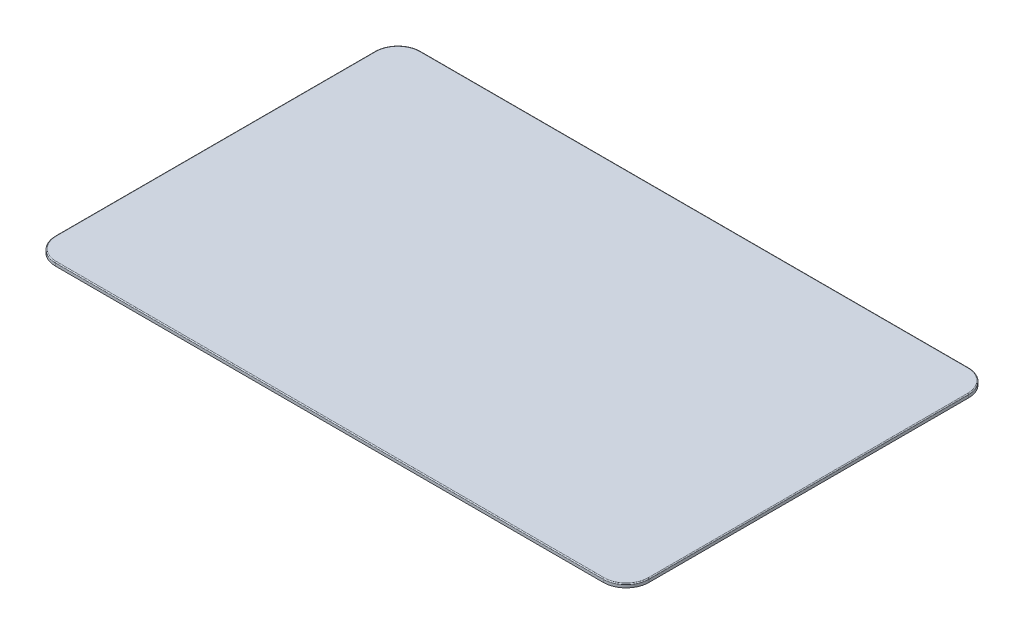
SolidWorks part; units mm, degrees
ref_plane "Спереди" through (0, 0, 0) normal (0, 0, 1) x (1, 0, 0)
ref_plane "Сверху" through (0, 0, 0) normal (0, 1, 0) x (1, 0, 0)
ref_plane "Справа" through (0, 0, 0) normal (1, 0, 0) x (0, 0, -1)
sketch "Эскиз1" plane through (0, 0, 0) normal (0, 1, 0) x (1, 0, 0)
  line L1 (-600, -400) -> (600, -400)
  line L2 (-650, -350) -> (-650, 350)
  line L3 (-600, 400) -> (600, 400)
  line L4 (650, -350) -> (650, 350)
  line L5 (-650, -400) -> (650, 400) construction
  line L6 (-650, 400) -> (650, -400) construction
  arc A0 (-600, 400) -> (-650, 350) centre (-600, 350) ccw
  arc A1 (600, 400) -> (650, 350) centre (600, 350) cw
  arc A2 (650, -350) -> (600, -400) centre (600, -350) cw
  arc A3 (-600, -400) -> (-650, -350) centre (-600, -350) cw
  point P0 (0, 0)
  dimension "D1" = 50
  dimension "D4" = 50
  dimension "D2" = 1300
  dimension "D3" = 800
extrude "Бобышка-Вытянуть1" add sketch "Эскиз1" along normal blind 8
fillet "Скругление1" radius 2 8 edges at (-635.3553, 8, -385.3553) (0, 8, -400) (635.3553, 8, -385.3553) (650, 8, 0) (635.3553, 8, 385.3553) (0, 8, 400) (-635.3553, 8, 385.3553) (-650, 8, 0)
sketch "Эскиз2" plane through (0, 0, 0) normal (0, -1, 0) x (1, 0, 0)
  line L0 (0, 398) -> (0, 115.0711) construction
  line L1 (-498, -35) -> (-405.9312, -35) construction
  line L2 (-494.82, 35) -> (-402.7512, 35) construction
  line L3 (-498, -100.1909) -> (-498, 80.8489) construction
  line L4 (-505.5, -118.7139) -> (-423, -118.7139)
  line L5 (-480.5, -93.7139) -> (-448, -93.7139)
  line L6 (-418, 113.7139) -> (-418, 29.5)
  line L7 (250, 398) -> (250, -398) construction
  line L8 (-250, 398) -> (-250, -398) construction
  line L9 (-648, 0) -> (648, 0) construction
  line L10 (302.5206, -212.9276) -> (307.7592, -212.906)
  line L12 (259.7408, -280.6043) -> (259.7408, -218.094)
  line L13 (262.2408, -283.1043) -> (308.0492, -283.1043)
  line L14 (265.5, -179.2861) -> (207.5, -179.2861)
  line L15 (-505.5, 118.7139) -> (-423, 118.7139)
  line L16 (-443, 88.7139) -> (-443, -88.7139)
  line L17 (-480.5, 93.7139) -> (-448, 93.7139)
  line L18 (-485.5, 84.9278) -> (-485.5, 88.7139)
  line L19 (-510.5, 85.0723) -> (-510.5, 113.7139)
  line L20 (-523.5388, 12.3957) -> (-523.2695, 77.6043)
  line L21 (403, -14.5) -> (302.5, -14.5)
  line L22 (403, 14.5) -> (302.5, 14.5)
  line L23 (418, -29.5) -> (418, -113.7139)
  line L24 (265.5, 174.2861) -> (207.5, 174.2861)
  line L25 (-515.5206, -80.0724) -> (-520.7592, -80.094)
  line L27 (270.5, -174.2861) -> (270.5, 169.2861)
  line L28 (197.4794, 212.9276) -> (192.2408, 212.906)
  line L29 (240.2592, 280.6043) -> (240.2592, 218.125)
  line L31 (237.7592, 283.1043) -> (191.9508, 283.1043)
  line L32 (250, 213.1446) -> (245.2798, 213.1251)
  line L33 (310.5388, -280.6043) -> (310.2695, -215.3957)
  line L34 (-472.7408, -12.3957) -> (-472.7408, -77.3957)
  line L35 (297.5, -207.9277) -> (297.5, -19.5)
  line L36 (202.5, -207.9277) -> (202.5, -184.2861)
  line L37 (-475.2408, 79.906) -> (-480.5206, 79.9278)
  line L38 (-302.5206, 212.9276) -> (-307.7592, 212.906)
  line L39 (-265.5, 179.2861) -> (-207.5, 179.2861)
  line L40 (-259.7408, 280.6043) -> (-259.7408, 218.1043)
  line L41 (189.4612, -280.6043) -> (189.7305, -215.3957)
  line L42 (-262.2408, 283.1043) -> (-308.0492, 283.1043)
  line L43 (-254.7408, 213.1043) -> (-245.2592, 213.1043)
  line L44 (237.7592, -283.1043) -> (191.9508, -283.1043)
  line L46 (240.2592, -280.6043) -> (240.2592, -218.094)
  line L47 (197.4794, -212.9276) -> (192.2408, -212.906)
  line L50 (-310.5388, 280.6043) -> (-310.2695, 215.3957)
  line L51 (-297.5, 207.9277) -> (-297.5, 14.5)
  line L52 (-202.5, 207.9277) -> (-202.5, 184.2861)
  line L53 (-189.4612, 280.6043) -> (-189.7305, 215.3957)
  line L54 (-265.5, -174.2861) -> (-207.5, -174.2861)
  line L56 (-475.2408, -9.8957) -> (-521.0492, -9.8957)
  line L57 (-475.2408, -79.906) -> (-480.5206, -79.9278)
  line L58 (-475.2408, 9.8957) -> (-521.0492, 9.8957)
  line L59 (-523.5388, -12.3957) -> (-523.2695, -77.6043)
  line L60 (-510.5, -85.0723) -> (-510.5, -113.7139)
  line L61 (-472.7408, 12.3957) -> (-472.7408, 77.3957)
  line L62 (-515.5206, 80.0724) -> (-520.7592, 80.094)
  line L63 (-485.5, -84.9278) -> (-485.5, -88.7139)
  line L65 (-197.4794, -212.9276) -> (-192.2408, -212.906)
  line L66 (-240.2592, -280.6043) -> (-240.2592, -218.125)
  line L68 (-237.7592, -283.1043) -> (-191.9508, -283.1043)
  line L69 (-250, -213.1446) -> (-245.2798, -213.1251)
  line L70 (485.5, -84.9278) -> (485.5, -88.7139)
  line L71 (-189.4612, -280.6043) -> (-189.7305, -215.3957)
  line L72 (-202.5, -207.9277) -> (-202.5, -179.2861)
  line L73 (-297.5, -207.9277) -> (-297.5, -14.5)
  line L74 (515.5206, 80.0724) -> (520.7592, 80.094)
  line L75 (472.7408, 12.3957) -> (472.7408, 77.3957)
  line L76 (510.5, -85.0723) -> (510.5, -113.7139)
  line L77 (523.5388, -12.3957) -> (523.2695, -77.6043)
  line L78 (475.2408, 9.8957) -> (521.0492, 9.8957)
  line L79 (475.2408, -79.906) -> (480.5206, -79.9278)
  line L80 (475.2408, -9.8957) -> (521.0492, -9.8957)
  line L81 (-102.1767, 35.0711) -> (-96.9381, 35.0927)
  line L82 (-142.4565, 34.9047) -> (-137.1767, 34.9265)
  line L83 (-94.1585, -32.6057) -> (-94.4278, 32.603)
  line L84 (-144.9565, -32.6056) -> (-144.9565, 32.3944)
  line L85 (-142.4565, -35.1056) -> (-96.6482, -35.1056)
  line L86 (-42.1767, 35.0711) -> (-36.9381, 35.0927)
  line L87 (-82.4565, 34.9047) -> (-77.1767, 34.9265)
  line L88 (-34.1585, -32.6057) -> (-34.4278, 32.603)
  line L89 (-84.9565, -32.6056) -> (-84.9565, 32.3944)
  line L90 (-82.4565, -35.1056) -> (-36.6482, -35.1056)
  line L91 (17.8233, 35.0711) -> (23.0619, 35.0927)
  line L92 (-22.4565, 34.9047) -> (-17.1767, 34.9265)
  line L93 (25.8415, -32.6057) -> (25.5722, 32.603)
  line L94 (-24.9565, -32.6056) -> (-24.9565, 32.3944)
  line L95 (-22.4565, -35.1056) -> (23.3518, -35.1056)
  line L96 (77.8233, 35.0711) -> (83.0619, 35.0927)
  line L97 (37.5435, 34.9047) -> (42.8233, 34.9265)
  line L98 (85.8415, -32.6057) -> (85.5722, 32.603)
  line L99 (35.0435, -32.6056) -> (35.0435, 32.3944)
  line L100 (37.5435, -35.1056) -> (83.3518, -35.1056)
  line L101 (137.9695, 35.0717) -> (143.0619, 35.0927)
  line L102 (97.5435, 34.9047) -> (102.0709, 34.9234)
  line L103 (145.8415, -32.6057) -> (145.5722, 32.603)
  line L104 (95.0435, -32.6056) -> (95.0435, 32.3944)
  line L105 (97.5435, -35.1056) -> (143.3518, -35.1056)
  line L106 (-132.1973, 39.9265) -> (-132.1973, 110.0711)
  line L107 (-107.1973, 40.071) -> (-107.1973, 85.0711)
  line L108 (0, 0) -> (0, -400) construction
  line L109 (67.8027, 80.0711) -> (17.8027, 80.0711)
  line L110 (107.1973, 40.071) -> (107.1973, 85.0711)
  line L112 (-310.5388, -280.6043) -> (-310.2695, -215.3957)
  line L114 (-237.7592, 283.1043) -> (-191.9508, 283.1043)
  line L116 (-240.2592, 280.6043) -> (-240.2592, 218.1043)
  line L117 (-197.4794, 212.9276) -> (-192.2408, 212.906)
  line L118 (-270.5, 174.2861) -> (-270.5, -169.2861)
  line L122 (-418, -29.5) -> (-418, -113.7139)
  line L123 (189.4612, 280.6043) -> (189.7305, 215.3957)
  line L124 (202.5, 207.9277) -> (202.5, 179.2861)
  line L125 (297.5, 207.9277) -> (297.5, 19.5)
  line L126 (310.5388, 280.6043) -> (310.2695, 215.3957)
  line L127 (250, 213.1446) -> (254.7202, 213.1251)
  line L128 (262.2408, 283.1043) -> (308.0492, 283.1043)
  line L129 (259.7408, 280.6043) -> (259.7408, 218.125)
  line L131 (302.5206, 212.9276) -> (307.7592, 212.906)
  line L132 (498, -100.1909) -> (498, 80.8489) construction
  line L133 (475.2408, 79.906) -> (480.5206, 79.9278)
  line L134 (472.7408, -12.3957) -> (472.7408, -77.3957)
  line L135 (515.5206, -80.0724) -> (520.7592, -80.094)
  line L136 (523.5388, 12.3957) -> (523.2695, 77.6043)
  line L137 (-403, 14.5) -> (-297.5, 14.5)
  line L138 (-403, -14.5) -> (-297.5, -14.5)
  line L139 (-250, -213.1446) -> (-254.7202, -213.1251)
  line L140 (510.5, 85.0723) -> (510.5, 113.7139)
  line L141 (485.5, 84.9278) -> (485.5, 88.7139)
  line L142 (-262.2408, -283.1043) -> (-308.0492, -283.1043)
  line L143 (494.82, 35) -> (402.7512, 35) construction
  line L144 (498, -35) -> (405.9312, -35) construction
  line L145 (480.5, 93.7139) -> (448, 93.7139)
  line L146 (443, 88.7139) -> (443, -88.7139)
  line L147 (505.5, 118.7139) -> (423, 118.7139)
  line L148 (418, 113.7139) -> (418, 29.5)
  line L149 (480.5, -93.7139) -> (448, -93.7139)
  line L150 (-259.7408, -280.6043) -> (-259.7408, -218.125)
  line L151 (505.5, -118.7139) -> (423, -118.7139)
  line L153 (-302.5206, -212.9276) -> (-307.7592, -212.906)
  line L154 (72.8027, 40.071) -> (72.8027, 50.0711)
  line L155 (47.8027, 39.9265) -> (47.8027, 50.0711)
  line L156 (12.8027, 40.071) -> (12.8027, 50.0711)
  line L157 (-12.1973, 39.9265) -> (-12.1973, 50.0711)
  line L158 (-47.1973, 40.071) -> (-47.1973, 50.0711)
  line L159 (-72.1973, 39.9265) -> (-72.1973, 50.0711)
  line L160 (254.7408, -213.094) -> (245.2592, -213.094)
  line L161 (42.8027, 55.0711) -> (17.8027, 55.0711)
  line L162 (-17.1973, 55.0711) -> (-42.1973, 55.0711)
  line L163 (102.1973, 90.0711) -> (17.1973, 90.0711)
  line L164 (72.8027, 50.0711) -> (72.8027, 75.0711)
  line L165 (-72.1973, 50.0711) -> (-72.1973, 75.0711)
  line L166 (127.8027, 115.0711) -> (-127.1973, 115.0711)
  line L167 (-102.1973, 90.0711) -> (-17.1973, 90.0711)
  line L170 (-17.1973, 80.0711) -> (-67.1973, 80.0711)
  line L171 (132.8027, 40.071) -> (132.8027, 110.0711)
  arc A0 (240.2592, -218.094) -> (245.2592, -213.094) centre (245.2592, -218.094) cw
  arc A1 (297.5, -207.9277) -> (302.5206, -212.9276) centre (302.5, -207.9277) ccw
  arc A2 (310.2695, -215.3957) -> (307.7592, -212.906) centre (310.2592, -212.8957) ccw
  arc A3 (259.7408, 218.125) -> (254.7202, 213.1251) centre (254.7408, 218.125) cw
  arc A4 (245.2798, 213.1251) -> (240.2592, 218.125) centre (245.2592, 218.125) cw
  arc A5 (202.5, -184.2861) -> (207.5, -179.2861) centre (207.5, -184.2861) cw
  arc A6 (308.0492, -283.1043) -> (310.5388, -280.6043) centre (310.5492, -283.1043) ccw
  arc A7 (259.7408, -280.6043) -> (262.2408, -283.1043) centre (259.7408, -283.1043) ccw
  arc A8 (240.2592, -280.6043) -> (237.7592, -283.1043) centre (240.2592, -283.1043) cw
  arc A9 (191.9508, -283.1043) -> (189.4612, -280.6043) centre (189.4508, -283.1043) cw
  arc A10 (270.5, 169.2861) -> (265.5, 174.2861) centre (265.5, 169.2861) ccw
  arc A11 (510.5, 113.7139) -> (505.5, 118.7139) centre (505.5, 113.7139) ccw
  arc A12 (265.5, -179.2861) -> (270.5, -174.2861) centre (265.5, -174.2861) ccw
  arc A13 (189.7305, -215.3957) -> (192.2408, -212.906) centre (189.7408, -212.8957) cw
  arc A14 (202.5, -207.9277) -> (197.4794, -212.9276) centre (197.5, -207.9277) cw
  arc A15 (254.7408, -213.094) -> (259.7408, -218.094) centre (254.7408, -218.094) cw
  arc A16 (-240.2592, 218.1043) -> (-245.2592, 213.1043) centre (-245.2592, 218.1043) cw
  arc A17 (505.5, -118.7139) -> (510.5, -113.7139) centre (505.5, -113.7139) ccw
  arc A18 (-254.7408, 213.1043) -> (-259.7408, 218.1043) centre (-254.7408, 218.1043) cw
  arc A19 (-202.5, 184.2861) -> (-207.5, 179.2861) centre (-207.5, 184.2861) cw
  arc A20 (413, 24.5) -> (418, 29.5) centre (413, 29.5) ccw
  arc A21 (202.5, 207.9277) -> (197.4794, 212.9276) centre (197.5, 207.9277) ccw
  arc A22 (189.7305, 215.3957) -> (192.2408, 212.906) centre (189.7408, 212.8957) ccw
  arc A23 (403, 14.5) -> (408, 19.5) centre (403, 19.5) ccw
  arc A24 (191.9508, 283.1043) -> (189.4612, 280.6043) centre (189.4508, 283.1043) ccw
  arc A25 (240.2592, 280.6043) -> (237.7592, 283.1043) centre (240.2592, 283.1043) ccw
  arc A26 (259.7408, 280.6043) -> (262.2408, 283.1043) centre (259.7408, 283.1043) cw
  arc A27 (308.0492, 283.1043) -> (310.5388, 280.6043) centre (310.5492, 283.1043) cw
  arc A28 (413, 24.5) -> (408, 19.5) centre (413, 19.5) ccw
  arc A29 (310.2695, 215.3957) -> (307.7592, 212.906) centre (310.2592, 212.8957) cw
  arc A30 (297.5, 207.9277) -> (302.5206, 212.9276) centre (302.5, 207.9277) cw
  arc A31 (413, -24.5) -> (408, -19.5) centre (413, -19.5) cw
  arc A32 (202.5, 179.2861) -> (207.5, 174.2861) centre (207.5, 179.2861) ccw
  arc A33 (-270.5, -169.2861) -> (-265.5, -174.2861) centre (-265.5, -169.2861) ccw
  arc A34 (485.5, 88.7139) -> (480.5, 93.7139) centre (480.5, 88.7139) ccw
  arc A35 (-443, -88.7139) -> (-448, -93.7139) centre (-448, -88.7139) cw
  arc A36 (480.5206, 79.9278) -> (485.5, 84.9278) centre (480.5, 84.9278) ccw
  arc A37 (510.5, 85.0723) -> (515.5206, 80.0724) centre (515.5, 85.0723) ccw
  arc A38 (472.7408, -12.3957) -> (475.2408, -9.8957) centre (472.7408, -9.8957) cw
  arc A39 (521.0492, -9.8957) -> (523.5388, -12.3957) centre (523.5492, -9.8957) cw
  arc A40 (475.2408, -79.906) -> (472.7408, -77.3957) centre (472.7408, -79.8957) cw
  arc A41 (523.2695, -77.6043) -> (520.7592, -80.094) centre (523.2592, -80.1043) cw
  arc A42 (510.5, -85.0723) -> (515.5206, -80.0724) centre (515.5, -85.0723) cw
  arc A43 (480.5206, -79.9278) -> (485.5, -84.9278) centre (480.5, -84.9278) cw
  arc A44 (523.2695, 77.6043) -> (520.7592, 80.094) centre (523.2592, 80.1043) ccw
  arc A45 (-418, -113.7139) -> (-423, -118.7139) centre (-423, -113.7139) cw
  arc A46 (485.5, -88.7139) -> (480.5, -93.7139) centre (480.5, -88.7139) cw
  arc A47 (475.2408, 79.906) -> (472.7408, 77.3957) centre (472.7408, 79.8957) ccw
  arc A48 (521.0492, 9.8957) -> (523.5388, 12.3957) centre (523.5492, 9.8957) ccw
  arc A49 (472.7408, 12.3957) -> (475.2408, 9.8957) centre (472.7408, 9.8957) ccw
  arc A50 (-443, 88.7139) -> (-448, 93.7139) centre (-448, 88.7139) ccw
  arc A51 (-418, 113.7139) -> (-423, 118.7139) centre (-423, 113.7139) ccw
  arc A52 (418, 113.7139) -> (423, 118.7139) centre (423, 113.7139) cw
  arc A53 (443, 88.7139) -> (448, 93.7139) centre (448, 88.7139) cw
  arc A54 (418, -113.7139) -> (423, -118.7139) centre (423, -113.7139) ccw
  arc A55 (443, -88.7139) -> (448, -93.7139) centre (448, -88.7139) ccw
  arc A56 (-472.7408, 12.3957) -> (-475.2408, 9.8957) centre (-472.7408, 9.8957) cw
  arc A57 (-521.0492, 9.8957) -> (-523.5388, 12.3957) centre (-523.5492, 9.8957) cw
  arc A58 (-475.2408, 79.906) -> (-472.7408, 77.3957) centre (-472.7408, 79.8957) cw
  arc A59 (-485.5, -88.7139) -> (-480.5, -93.7139) centre (-480.5, -88.7139) ccw
  arc A60 (-523.2695, 77.6043) -> (-520.7592, 80.094) centre (-523.2592, 80.1043) cw
  arc A61 (-480.5206, -79.9278) -> (-485.5, -84.9278) centre (-480.5, -84.9278) ccw
  arc A62 (-510.5, -85.0723) -> (-515.5206, -80.0724) centre (-515.5, -85.0723) ccw
  arc A63 (-523.2695, -77.6043) -> (-520.7592, -80.094) centre (-523.2592, -80.1043) ccw
  arc A64 (-475.2408, -79.906) -> (-472.7408, -77.3957) centre (-472.7408, -79.8957) ccw
  arc A65 (-521.0492, -9.8957) -> (-523.5388, -12.3957) centre (-523.5492, -9.8957) ccw
  arc A66 (-472.7408, -12.3957) -> (-475.2408, -9.8957) centre (-472.7408, -9.8957) ccw
  arc A67 (-510.5, 85.0723) -> (-515.5206, 80.0724) centre (-515.5, 85.0723) cw
  arc A68 (-480.5206, 79.9278) -> (-485.5, 84.9278) centre (-480.5, 84.9278) cw
  arc A69 (-485.5, 88.7139) -> (-480.5, 93.7139) centre (-480.5, 88.7139) cw
  arc A70 (-202.5, -179.2861) -> (-207.5, -174.2861) centre (-207.5, -179.2861) ccw
  arc A71 (-270.5, 174.2861) -> (-265.5, 179.2861) centre (-265.5, 174.2861) cw
  arc A72 (297.5, 19.5) -> (302.5, 14.5) centre (302.5, 19.5) ccw
  arc A73 (-297.5, 207.9277) -> (-302.5206, 212.9276) centre (-302.5, 207.9277) ccw
  arc A74 (-310.2695, 215.3957) -> (-307.7592, 212.906) centre (-310.2592, 212.8957) ccw
  arc A75 (297.5, -19.5) -> (302.5, -14.5) centre (302.5, -19.5) cw
  arc A76 (-308.0492, 283.1043) -> (-310.5388, 280.6043) centre (-310.5492, 283.1043) ccw
  arc A77 (-259.7408, 280.6043) -> (-262.2408, 283.1043) centre (-259.7408, 283.1043) ccw
  arc A78 (-240.2592, 280.6043) -> (-237.7592, 283.1043) centre (-240.2592, 283.1043) cw
  arc A79 (-191.9508, 283.1043) -> (-189.4612, 280.6043) centre (-189.4508, 283.1043) cw
  arc A80 (-418, -29.5) -> (-413, -24.5) centre (-413, -29.5) cw
  arc A81 (-189.7305, 215.3957) -> (-192.2408, 212.906) centre (-189.7408, 212.8957) cw
  arc A82 (-202.5, 207.9277) -> (-197.4794, 212.9276) centre (-197.5, 207.9277) cw
  arc A83 (-403, -14.5) -> (-408, -19.5) centre (-403, -19.5) ccw
  arc A84 (-240.2592, -218.125) -> (-245.2798, -213.1251) centre (-245.2592, -218.125) ccw
  arc A85 (-254.7202, -213.1251) -> (-259.7408, -218.125) centre (-254.7408, -218.125) ccw
  arc A86 (-505.5, -118.7139) -> (-510.5, -113.7139) centre (-505.5, -113.7139) cw
  arc A87 (403, -14.5) -> (408, -19.5) centre (403, -19.5) cw
  arc A88 (413, -24.5) -> (418, -29.5) centre (413, -29.5) cw
  arc A89 (-202.5, -207.9277) -> (-197.4794, -212.9276) centre (-197.5, -207.9277) ccw
  arc A90 (-189.7305, -215.3957) -> (-192.2408, -212.906) centre (-189.7408, -212.8957) ccw
  arc A91 (-418, 29.5) -> (-413, 24.5) centre (-413, 29.5) ccw
  arc A92 (-510.5, 113.7139) -> (-505.5, 118.7139) centre (-505.5, 113.7139) cw
  arc A93 (-403, 14.5) -> (-408, 19.5) centre (-403, 19.5) cw
  arc A94 (-191.9508, -283.1043) -> (-189.4612, -280.6043) centre (-189.4508, -283.1043) ccw
  arc A95 (-240.2592, -280.6043) -> (-237.7592, -283.1043) centre (-240.2592, -283.1043) ccw
  arc A96 (-259.7408, -280.6043) -> (-262.2408, -283.1043) centre (-259.7408, -283.1043) cw
  arc A97 (-308.0492, -283.1043) -> (-310.5388, -280.6043) centre (-310.5492, -283.1043) cw
  arc A98 (-408, 19.5) -> (-413, 24.5) centre (-413, 19.5) ccw
  arc A99 (-413, -24.5) -> (-408, -19.5) centre (-413, -19.5) ccw
  arc A101 (-310.2695, -215.3957) -> (-307.7592, -212.906) centre (-310.2592, -212.8957) cw
  arc A102 (-297.5, -207.9277) -> (-302.5206, -212.9276) centre (-302.5, -207.9277) cw
  arc A104 (-137.1767, 34.9265) -> (-132.1973, 39.9265) centre (-137.1973, 39.9265) ccw
  arc A105 (-144.9565, -32.6056) -> (-142.4565, -35.1056) centre (-144.9565, -35.1056) ccw
  arc A106 (-107.1973, 40.071) -> (-102.1767, 35.0711) centre (-102.1973, 40.071) ccw
  arc A107 (-94.4278, 32.603) -> (-96.9381, 35.0927) centre (-94.4381, 35.103) ccw
  arc A108 (-142.4565, 34.9047) -> (-144.9565, 32.3944) centre (-144.9565, 34.8944) ccw
  arc A109 (-96.6482, -35.1056) -> (-94.1585, -32.6057) centre (-94.1482, -35.1056) ccw
  arc A110 (-77.1767, 34.9265) -> (-72.1973, 39.9265) centre (-77.1973, 39.9265) ccw
  arc A111 (-84.9565, -32.6056) -> (-82.4565, -35.1056) centre (-84.9565, -35.1056) ccw
  arc A112 (-47.1973, 40.071) -> (-42.1767, 35.0711) centre (-42.1973, 40.071) ccw
  arc A113 (-34.4278, 32.603) -> (-36.9381, 35.0927) centre (-34.4381, 35.103) ccw
  arc A114 (-82.4565, 34.9047) -> (-84.9565, 32.3944) centre (-84.9565, 34.8944) ccw
  arc A115 (-36.6482, -35.1056) -> (-34.1585, -32.6057) centre (-34.1482, -35.1056) ccw
  arc A116 (-17.1767, 34.9265) -> (-12.1973, 39.9265) centre (-17.1973, 39.9265) ccw
  arc A117 (-24.9565, -32.6056) -> (-22.4565, -35.1056) centre (-24.9565, -35.1056) ccw
  arc A118 (12.8027, 40.071) -> (17.8233, 35.0711) centre (17.8027, 40.071) ccw
  arc A119 (25.5722, 32.603) -> (23.0619, 35.0927) centre (25.5619, 35.103) ccw
  arc A120 (-22.4565, 34.9047) -> (-24.9565, 32.3944) centre (-24.9565, 34.8944) ccw
  arc A121 (23.3518, -35.1056) -> (25.8415, -32.6057) centre (25.8518, -35.1056) ccw
  arc A122 (42.8233, 34.9265) -> (47.8027, 39.9265) centre (42.8027, 39.9265) ccw
  arc A123 (35.0435, -32.6056) -> (37.5435, -35.1056) centre (35.0435, -35.1056) ccw
  arc A124 (72.8027, 40.071) -> (77.8233, 35.0711) centre (77.8027, 40.071) ccw
  arc A125 (85.5722, 32.603) -> (83.0619, 35.0927) centre (85.5619, 35.103) ccw
  arc A126 (37.5435, 34.9047) -> (35.0435, 32.3944) centre (35.0435, 34.8944) ccw
  arc A127 (83.3518, -35.1056) -> (85.8415, -32.6057) centre (85.8518, -35.1056) ccw
  arc A128 (102.0709, 34.9234) -> (107.1973, 40.071) centre (102.0497, 40.071) ccw
  arc A129 (95.0435, -32.6056) -> (97.5435, -35.1056) centre (95.0435, -35.1056) ccw
  arc A130 (132.8027, 40.071) -> (137.9695, 35.0717) centre (137.9482, 40.2193) ccw
  arc A131 (145.5722, 32.603) -> (143.0619, 35.0927) centre (145.5619, 35.103) ccw
  arc A132 (97.5435, 34.9047) -> (95.0435, 32.3944) centre (95.0435, 34.8944) ccw
  arc A133 (143.3518, -35.1056) -> (145.8415, -32.6057) centre (145.8518, -35.1056) ccw
  arc A134 (17.1973, 90.0711) -> (17.8027, 80.0711) centre (17.1973, 85.0527) ccw
  arc A135 (-17.1973, 80.0711) -> (-17.1973, 90.0711) centre (-17.1973, 85.0711) ccw
  arc A136 (-42.1973, 55.0711) -> (-47.1973, 50.0711) centre (-42.1973, 50.0711) ccw
  arc A137 (-17.1973, 55.0711) -> (-12.1973, 50.0711) centre (-17.1973, 50.0711) cw
  arc A138 (17.8027, 55.0711) -> (12.8027, 50.0711) centre (17.8027, 50.0711) ccw
  arc A139 (47.8027, 50.0711) -> (42.8027, 55.0711) centre (42.8027, 50.0711) ccw
  arc A140 (-72.1973, 75.0711) -> (-67.1973, 80.0711) centre (-67.1973, 75.0711) cw
  arc A141 (107.1973, 85.0711) -> (102.1973, 90.0711) centre (102.1973, 85.0711) ccw
  arc A142 (127.8027, 115.0711) -> (132.8027, 110.0711) centre (127.8027, 110.0711) cw
  arc A143 (-107.1973, 85.0711) -> (-102.1973, 90.0711) centre (-102.1973, 85.0711) cw
  arc A144 (-127.1973, 115.0711) -> (-132.1973, 110.0711) centre (-127.1973, 110.0711) ccw
  arc A145 (67.8027, 80.0711) -> (72.8027, 75.0711) centre (67.8027, 75.0711) cw
  point P24 (285, -248)
  point P39 (285, -213)
  point P75 (202.5, -179.2861)
  point P79 (0, 0)
  point P84 (60, 0)
  point P85 (-119.6973, -0.0013)
  point P86 (-119.6973, 34.9987)
  point P89 (120, 0)
  point P94 (-60, 0)
  point P99 (-120, 0)
  point P139 (215, -213)
  point P140 (215, -248)
  point P141 (250, -186.7861)
  point P142 (250, -186.7861)
  point P144 (-240.2592, 213.1043)
  point P148 (-259.7408, 213.1043)
  point P199 (250, 186.7861)
  point P200 (215, 248)
  point P201 (215, 213)
  point P202 (285, 213)
  point P203 (285, 248)
  point P241 (498, -80)
  point P242 (498, -45)
  point P243 (463, -106.2139)
  point P244 (463, -106.2139)
  point P267 (-202.5, 179.2861)
  point P268 (463, 106.2139)
  point P269 (498, 45)
  point P270 (498, 80)
  point P384 (-498, 80)
  point P385 (-498, 45)
  point P388 (-463, 106.2139)
  point P389 (-463, -106.2139)
  point P390 (-498, -45)
  point P391 (-498, -80)
  point P392 (-285, 248)
  point P393 (-285, 213)
  point P394 (-215, 213)
  point P395 (-215, 248)
  point P396 (-250, 186.7861)
  point P397 (-250, -186.7861)
  point P398 (-215, -248)
  point P399 (-215, -213)
  point P400 (-285, -213)
  point P401 (-285, -248)
  point P406 (-59.6973, -0.0013)
  point P407 (-59.6973, 34.9987)
  point P426 (0.3027, -0.0013)
  point P427 (0.3027, 34.9987)
  point P446 (60.3027, -0.0013)
  point P447 (60.3027, 34.9987)
  point P466 (120.3027, -0.0013)
  point P467 (120.3027, 34.9987)
  point P494 (-107.1973, 55.0711)
  point P497 (-72.1973, 55.0711)
  point P500 (-47.1973, 55.0711)
  point P503 (-12.1973, 55.0711)
  point P506 (12.8027, 55.0711)
  point P509 (47.8027, 55.0711)
  point P518 (0.3027, 80.0711)
  dimension "D2" = 5
  dimension "D3" = 5
  dimension "D4" = 5
  dimension "D6" = 5
  dimension "D7" = 5
  dimension "D8" = 5
  dimension "D9" = 5
  dimension "D10" = 5.1477
  dimension "D11" = 5
  dimension "D12" = 5
  dimension "D13" = 5
  dimension "D14" = 5
  dimension "D15" = 5
  dimension "D16" = 5
  dimension "D17" = 5
  dimension "D18" = 5
  dimension "D19" = 5
  dimension "D20" = 5
  dimension "D5" = 5
  dimension "D21" = 5
  dimension "D22" = 5
  dimension "D23" = 5
  dimension "D24" = 5
  dimension "D25" = 5
extrude "Вырез-Вытянуть1" cut sketch "Эскиз2" against normal blind 6
